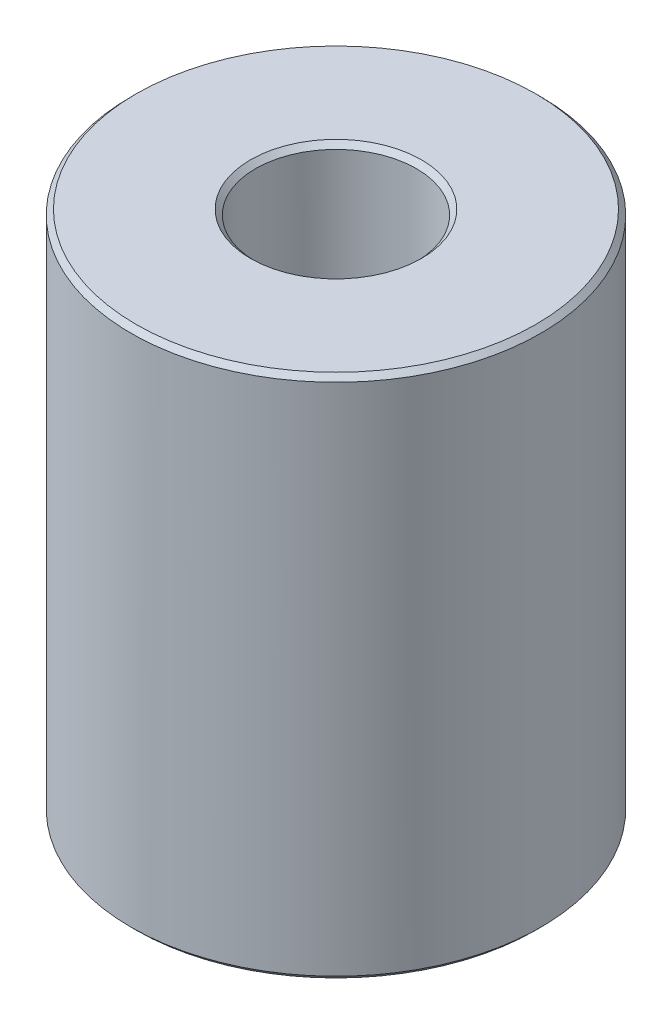
SolidWorks part; units mm, degrees
ref_plane "Front Plane" through (0, 0, 0) normal (0, 0, 1) x (1, 0, 0)
ref_plane "Top Plane" through (0, 0, 0) normal (0, 1, 0) x (1, 0, 0)
ref_plane "Right Plane" through (0, 0, 0) normal (1, 0, 0) x (0, 0, -1)
sketch "Sketch1" plane through (0, 0, 0) normal (0, 1, 0) x (1, 0, 0)
  circle A0 centre (0, 0) radius 57.5
  dimension "SLEEVE_OD" = 115
extrude "Boss-Extrude1" add sketch "Sketch1" along normal blind 147.2173
sketch "Sketch2" plane through (0, 0, 0) normal (0, 1, 0) x (1, 0, 0)
  circle A0 centre (0, 0) radius 22.5675
  dimension "BORE_D" = 45.1349
extrude "Cut-Extrude1" cut sketch "Sketch2" along normal through all
chamfer "Chamfer1" distance 1.431 angle 45 4 edges at (0, 147.2173, 22.5675) (0, 0, 22.5675) (0, 0, 57.5) (0, 147.2173, 57.5)
